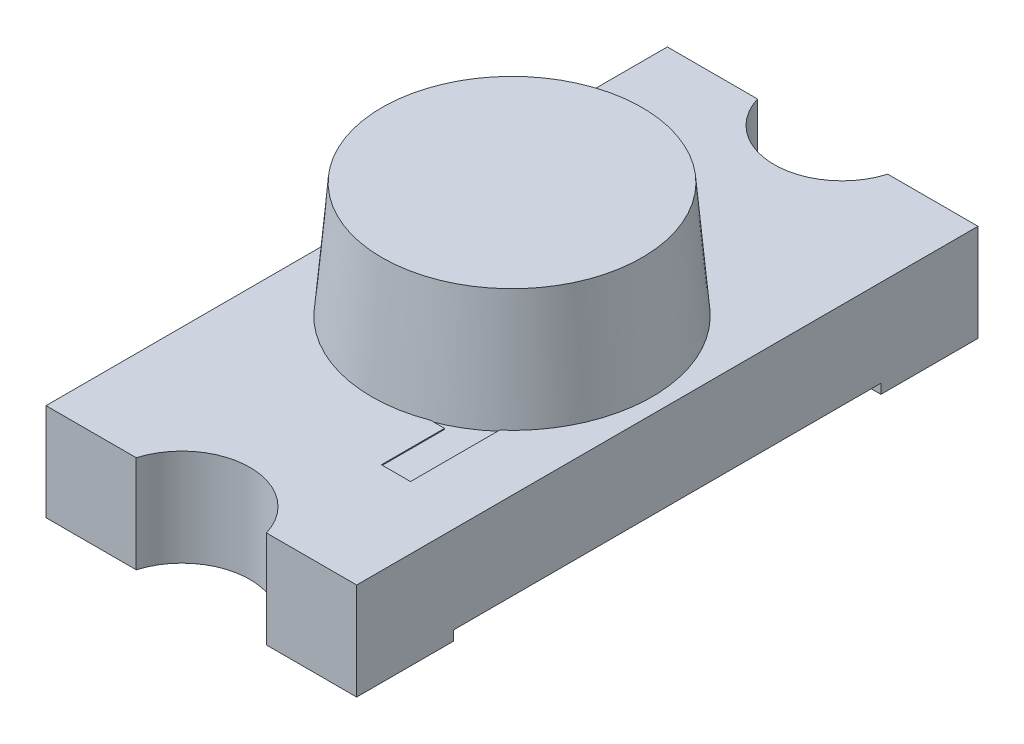
SolidWorks part; units mm, degrees
ref_plane "Front Plane" through (0, 0, 0) normal (0, 0, 1) x (1, 0, 0)
ref_plane "Top Plane" through (0, 0, 0) normal (0, 1, 0) x (1, 0, 0)
ref_plane "Right Plane" through (0, 0, 0) normal (1, 0, 0) x (0, 0, -1)
sketch "Sketch1" plane through (0, 0, 0) normal (1, 0, 0) x (0, 0, -1)
  line L0 (1.1, 0) -> (1.6, 0)
  line L1 (-1.6, 0.5) -> (1.6, 0.5)
  line L2 (-1.6, 0.5) -> (-1.6, 0)
  line L3 (-1.6, 0) -> (-1.1, 0)
  line L4 (1.6, 0.5) -> (1.6, 0)
  line L5 (-1.1, 0.05) -> (1.1, 0.05)
  line L6 (-1.1, 0.05) -> (-1.1, 0)
  line L8 (1.1, 0.05) -> (1.1, 0)
  dimension "D1" = 3.2
  dimension "D2" = 0.5
  dimension "D3" = 0.05
  dimension "D4" = 2.2
  dimension "D5" = 1.1
extrude "Extrude1" add sketch "Sketch1" along normal blind 0.8 and the other way blind 0.8
sketch "Sketch2" plane through (0, 0, 0) normal (0, 1, 0) x (1, 0, 0)
  circle A0 centre (0, 1.7) radius 0.35
  circle A1 centre (0, -1.7) radius 0.35
extrude "Cut-Extrude1" cut sketch "Sketch2" along normal through all
sketch "Sketch3" plane through (0, 0.5, 0) normal (0, 1, 0) x (-1, 0, 0)
  line L1 (0.4574, -1) -> (0.2774, -1)
  line L2 (0.4574, -1) -> (0.4574, -0.4507)
  line L3 (0.225, -0.225) -> (-0.225, -0.225)
  line L4 (0.2774, -1) -> (0.2774, -0.6307)
  line L5 (0.4574, -0.4507) -> (-0.2764, -0.4507)
  line L7 (0.2774, -0.6307) -> (-0.2764, -0.6307)
  line L8 (-0.2764, -0.4507) -> (-0.2764, -0.6307)
  line L9 (0.225, -0.225) -> (0.225, 0.4637)
  line L10 (0.075, 0.225) -> (-0.225, 0.225)
  line L11 (-0.225, -0.225) -> (-0.225, 0.225)
  line L13 (0.225, 0.4637) -> (0.225, 0.7354)
  line L15 (0.075, 0.225) -> (0.075, 0.525)
  line L16 (0.075, 0.525) -> (-0.2794, 0.525)
  line L17 (0.225, 0.7354) -> (0.225, 0.675)
  line L18 (0.225, 0.675) -> (-0.3274, 0.675)
  line L20 (-0.2794, 0.525) -> (-0.4774, 0.525)
  line L21 (-0.3274, 0.675) -> (-0.3274, 1)
  line L22 (-0.3274, 1) -> (-0.4774, 1)
  line L23 (-0.4774, 0.525) -> (-0.4774, 1)
  dimension "D1" = 0.45
  dimension "D2" = 0.45
  dimension "D3" = 0.225
  dimension "D4" = 0.225
  dimension "D5" = 0.15
  dimension "D6" = 0.15
  dimension "D7" = 0.15
  dimension "D8" = 0.3
  dimension "D9" = 1
  dimension "D10" = 1
  dimension "D11" = 0.18
  dimension "D12" = 0.18
extrude "Cut-Extrude2" cut sketch "Sketch3" against normal blind 0.005 contours L23 L20 L16 L15 L10 L11 L3 L9 L13 L18 L21 L22 | L5 L8 L7 L4 L1 L2 region at (-0.3674, 0.5, -0.9908) region at (0, 0.5, -0.2109)
sketch "Sketch4" plane through (0, 0.495, 0) normal (0, 1, 0) x (-1, 0, 0)
  line L1 (0.195, -0.195) -> (-0.195, -0.195)
  line L2 (0.195, -0.195) -> (0.195, 0.195)
  line L3 (0.195, 0.195) -> (-0.195, 0.195)
  line L4 (-0.195, -0.195) -> (-0.195, 0.195)
  dimension "D1" = 0.39
  dimension "D2" = 0.39
  dimension "D3" = 0.195
  dimension "D4" = 0.195
extrude "Extrude2" add sketch "Sketch4" along normal blind 0.25
sketch "Sketch5" plane through (0, 0.495, 0) normal (0, 1, 0) x (-1, 0, 0)
  circle A0 centre (0, 0) radius 0.7223
extrude "Extrude3" add sketch "Sketch5" along normal blind 0.6 draft 5 separate body
sketch "Component_Outline" plane through (0, 0, 0) normal (0, 1, 0) x (1, 0, 0)
  line L0 (0.3354, 1.6) -> (0.8, 1.6)
  line L1 (-0.8, -1.6) -> (-0.3354, -1.6)
  line L2 (-0.8, -1.6) -> (-0.8, 1.6)
  line L3 (-0.8, 1.6) -> (-0.3354, 1.6)
  line L4 (0.8, -1.6) -> (0.8, 1.6)
  line L5 (0.3354, -1.6) -> (0.8, -1.6)
  arc A0 (-0.3354, 1.6) -> (0.3354, 1.6) centre (0, 1.7) ccw
  arc A1 (-0.3354, 1.6) -> (0.3354, 1.6) centre (0, 1.7) ccw construction
  arc A2 (-0.3354, -1.6) -> (0.3354, -1.6) centre (0, -1.7) cw
  arc A3 (0.3354, -1.6) -> (-0.3354, -1.6) centre (0, -1.7) ccw construction
